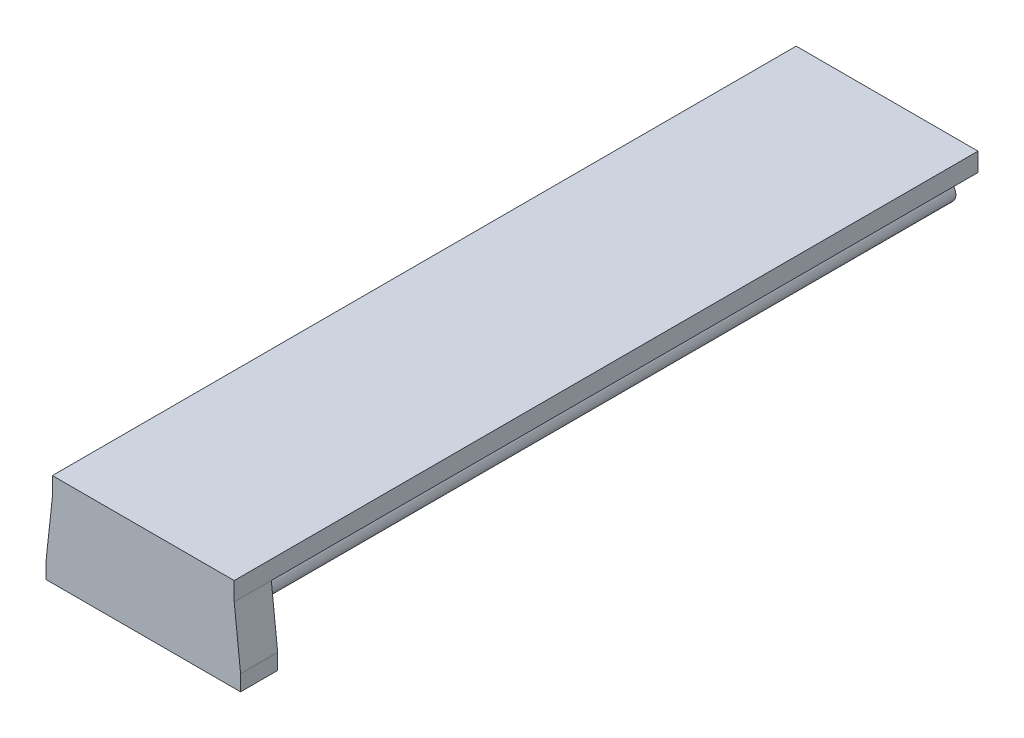
SolidWorks part; units mm, degrees
ref_plane "Front Plane" through (0, 0, 0) normal (0, 0, 1) x (1, 0, 0)
ref_plane "Top Plane" through (0, 0, 0) normal (0, 1, 0) x (1, 0, 0)
ref_plane "Right Plane" through (0, 0, 0) normal (1, 0, 0) x (0, 0, -1)
sketch "Sketch1" plane through (0, 0, 0) normal (0, 0, 1) x (1, 0, 0)
  line L9 (-3.2512, 11.4294) -> (-3.2512, 11.7608)
  line L10 (4.1904, 12.7) -> (5.2436, 12.7)
  line L11 (3.2512, 11.4294) -> (3.2512, 11.7608)
  line L12 (6.3485, 10.4902) -> (4.1904, 10.4902)
  line L13 (3.7373, 5.2999) -> (7.1039, 8.6665)
  line L14 (-2.164, 4.6482) -> (2.164, 4.6482)
  line L15 (-4.1904, 12.7) -> (-5.2436, 12.7)
  line L16 (-6.3485, 10.4902) -> (-4.1904, 10.4902)
  line L17 (-3.7373, 5.2999) -> (-7.1039, 8.6665)
  line L18 (-5.2436, 12.7) -> (-9.8037, 12.7)
  line L19 (5.2436, 12.7) -> (6.3485, 12.7)
  line L20 (6.3485, 12.7) -> (9.8037, 12.7)
  line L21 (9.8037, 12.7) -> (9.8037, 14.7)
  line L22 (9.8037, 14.7) -> (-9.8037, 14.7)
  line L23 (-9.8037, 14.7) -> (-9.8037, 12.7)
  line L24 (-9.8037, 12.7) -> (-10.4902, 6.3485)
  line L25 (-10.4902, 6.3485) -> (-10.4902, 4.6482)
  line L27 (-10.4902, 4.6482) -> (10.4902, 4.6482)
  line L30 (10.4902, 4.6482) -> (10.4902, 6.3485)
  line L31 (10.4902, 6.3485) -> (9.8037, 12.7)
  arc A8 (4.1904, 12.7) -> (3.2512, 11.7608) centre (4.1904, 11.7608) ccw
  arc A9 (3.2512, 11.4294) -> (4.1904, 10.4902) centre (4.1904, 11.4294) ccw
  arc A10 (7.1039, 8.6665) -> (6.3485, 10.4902) centre (6.3485, 9.4219) ccw
  arc A11 (2.164, 4.6482) -> (3.7373, 5.2999) centre (2.164, 6.8732) ccw
  arc A12 (-3.7373, 5.2999) -> (-2.164, 4.6482) centre (-2.164, 6.8732) ccw
  arc A13 (-3.2512, 11.7608) -> (-4.1904, 12.7) centre (-4.1904, 11.7608) ccw
  arc A14 (-4.1904, 10.4902) -> (-3.2512, 11.4294) centre (-4.1904, 11.4294) ccw
  arc A15 (-6.3485, 10.4902) -> (-7.1039, 8.6665) centre (-6.3485, 9.4219) ccw
  dimension "D1" = 2
  dimension "D2" = 20.9804
extrude "Boss-Extrude1" add sketch "Sketch1" against normal blind 76.2 contours L16 A15 L17 A12 L14 A11 L13 A10 L12 A9 L11 A8 L10 L19 L20 L21 L22 L23 L18 L15 A13 L9 A14 region at (0, 10.271, 0)
extrude "Boss-Extrude2" add sketch "Sketch1<3>" along normal blind 4 contours A15 L16 A14 L9 A13 L15 L18 L24 L25 L27 A12 L17 | L16 A15 L17 A12 L14 A11 L13 A10 L12 A9 L11 A8 L10 L19 L20 L21 L22 L23 L18 L15 A13 L9 A14 | A11 L27 L30 L31 L20 L19 L10 A8 L11 A9 L12 A10 L13 region at (-7.4188, 8.6105, 0) region at (0, 10.271, 0) region at (7.4188, 8.6105, 0)
sketch "Sketch1<3>" plane through (0, 0, 0) normal (0, 0, 1) x (1, 0, 0) same geometry as "Sketch1"
